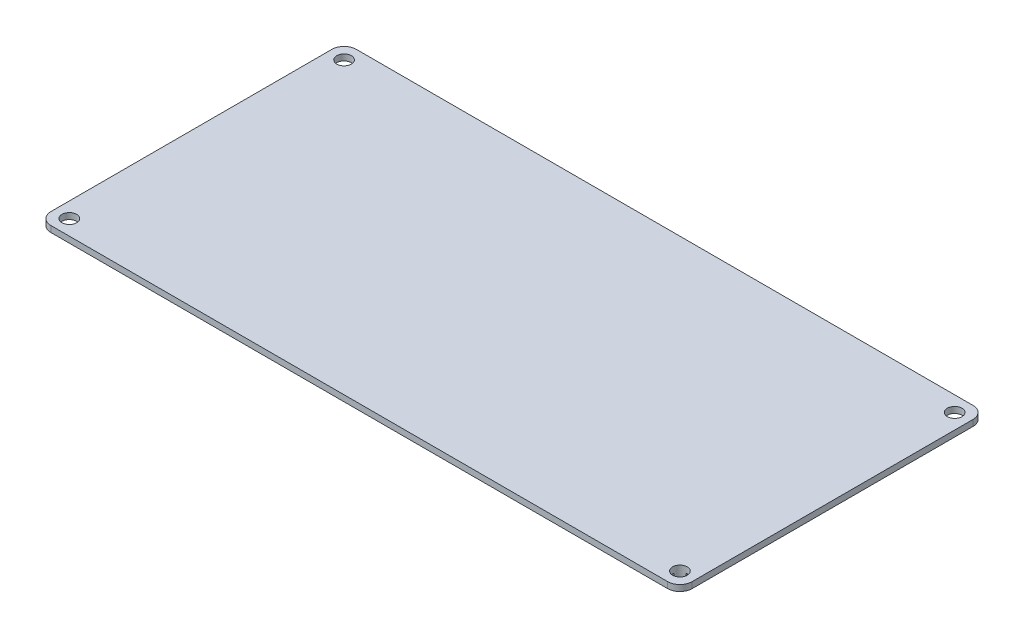
SolidWorks part; units mm, degrees
material "PLA/ABS"
ref_plane "Front Plane" through (0, 0, 0) normal (0, 0, 1) x (1, 0, 0)
ref_plane "Top Plane" through (0, 0, 0) normal (0, 1, 0) x (1, 0, 0)
ref_plane "Right Plane" through (0, 0, 0) normal (1, 0, 0) x (0, 0, -1)
sketch "Sketch2" plane through (0, 0, 0) normal (0, 1, 0) x (1, 0, 0)
  line L1 (-63.5, 28.575) -> (63.5, 28.575)
  line L2 (-63.5, 28.575) -> (-63.5, -28.575)
  line L3 (-63.5, -28.575) -> (63.5, -28.575)
  line L4 (63.5, 28.575) -> (63.5, -28.575)
  line L5 (-63.5, 28.575) -> (63.5, -28.575) construction
  line L6 (-63.5, -28.575) -> (63.5, 28.575) construction
  point P0 (0, 0)
  dimension "D1" = 57.15
  dimension "D2" = 127
extrude "Boss-Extrude3" add sketch "Sketch2" along normal blind 1.27
sketch "Sketch3" plane through (0, 1.27, 0) normal (0, 1, 0) x (1, 0, 0)
  line L0 (63.5, 28.575) -> (-63.5, 28.575) construction
  line L1 (-66.675, 31.75) -> (66.675, 31.75)
  line L2 (-66.675, 31.75) -> (-66.675, -31.75)
  line L3 (-66.675, -31.75) -> (66.675, -31.75)
  line L4 (66.675, 31.75) -> (66.675, -31.75)
  line L5 (-66.675, 31.75) -> (66.675, -31.75) construction
  line L6 (-66.675, -31.75) -> (66.675, 31.75) construction
  line L7 (63.5, -28.575) -> (63.5, 28.575) construction
  point P0 (0, 0)
  dimension "D1" = 3.175
  dimension "D2" = 3.175
extrude "Boss-Extrude4" add sketch "Sketch3" along normal blind 1.27
sketch "Sketch4" plane through (0, 0, 0) normal (0, -1, 0) x (-1, 0, 0)
  circle A0 centre (63.5, -28.575) radius 1.524
  circle A1 centre (-63.5, -28.575) radius 1.524
  circle A2 centre (-63.5, 28.575) radius 1.524
  circle A3 centre (63.5, 28.575) radius 1.524
  dimension "D1" = 3.048
extrude "Cut-Extrude1" cut sketch "Sketch4" against normal through all
fillet "Fillet1" radius 2.54 4 edges at (-66.675, 1.905, 31.75) (-66.675, 1.905, -31.75) (66.675, 1.905, -31.75) (66.675, 1.905, 31.75)
sketch "Sketch5" plane through (0, 0, 0) normal (0, -1, 0) x (-1, 0, 0)
  line L0 (-63.5, -27.051) -> (-63.5, 27.051) construction
  line L1 (63.2714, -28.3464) -> (-63.2714, -28.3464)
  line L2 (63.2714, -28.3464) -> (63.2714, 28.3464)
  line L3 (63.2714, 28.3464) -> (-63.2714, 28.3464)
  line L4 (-63.2714, -28.3464) -> (-63.2714, 28.3464)
  line L5 (63.2714, -28.3464) -> (-63.2714, 28.3464) construction
  line L6 (63.2714, 28.3464) -> (-63.2714, -28.3464) construction
  line L7 (-61.976, 28.575) -> (61.976, 28.575) construction
  line L8 (-61.976, 28.575) -> (61.976, 28.575) construction
  line L9 (63.5, -28.575) -> (-63.5, -28.575)
  line L10 (63.5, -28.575) -> (63.5, 28.575)
  line L11 (63.5, 28.575) -> (-63.5, 28.575)
  line L12 (-63.5, -28.575) -> (-63.5, 28.575)
  line L13 (63.5, -28.575) -> (-63.5, 28.575) construction
  line L14 (63.5, 28.575) -> (-63.5, -28.575) construction
  line L15 (-63.5, -27.051) -> (-63.5, 27.051) construction
  point P0 (0, 0)
  point P10 (0, 0)
  dimension "D1" = 0.2286
  dimension "D2" = 0.2286
extrude "Cut-Extrude2" cut sketch "Sketch5" against normal up to surface (1.27 mm away) up to face at (0, 1.27, 0)
